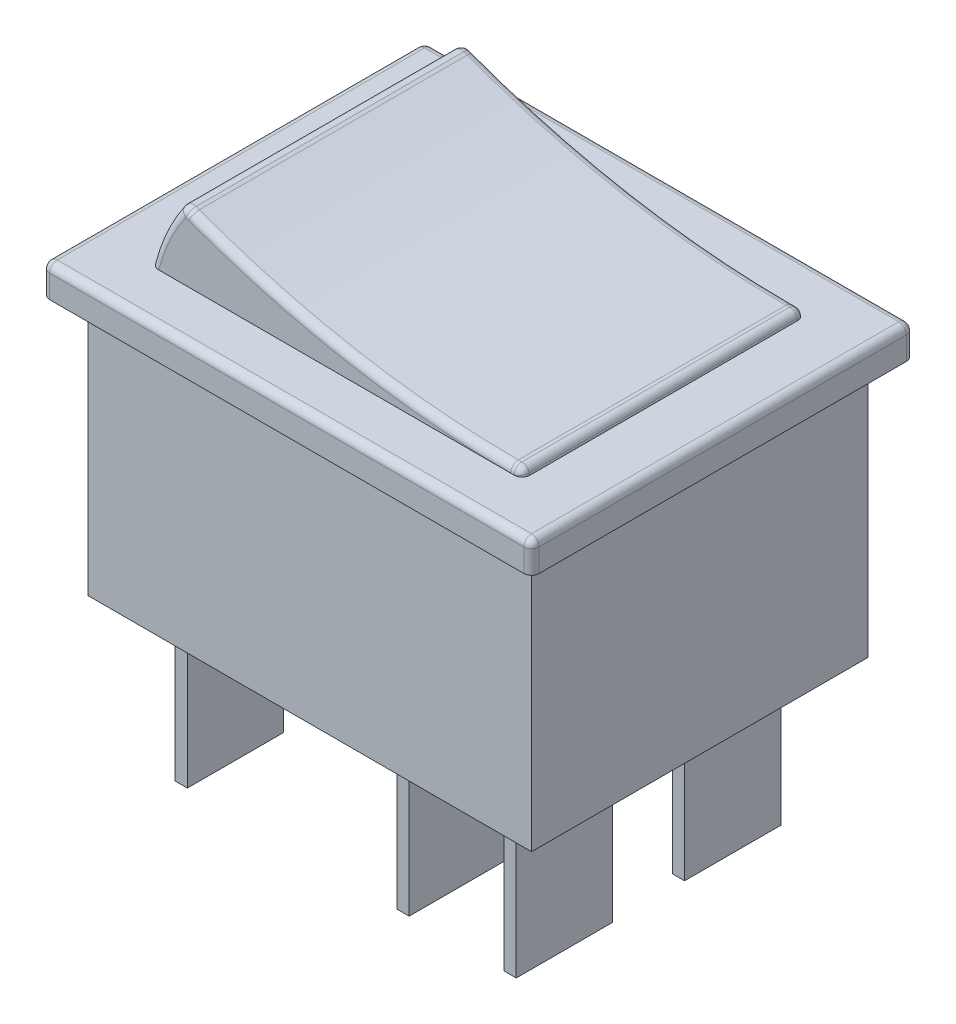
SolidWorks part; units mm, degrees
material "ABS"
ref_plane "Plan de face" through (0, 0, 0) normal (0, 0, 1) x (1, 0, 0)
ref_plane "Plan de dessus" through (0, 0, 0) normal (0, 1, 0) x (1, 0, 0)
ref_plane "Plan de droite" through (0, 0, 0) normal (1, 0, 0) x (0, 0, -1)
sketch "Esquisse1" plane through (0, 0, 0) normal (0, 1, 0) x (1, 0, 0)
  line L1 (-16, -12.5) -> (16, -12.5)
  line L2 (-16, -12.5) -> (-16, 12.5)
  line L3 (-16, 12.5) -> (16, 12.5)
  line L4 (16, -12.5) -> (16, 12.5)
  line L5 (-16, -12.5) -> (16, 12.5) construction
  line L6 (-16, 12.5) -> (16, -12.5) construction
  point P0 (0, 0)
  dimension "D1" = 25
  dimension "D2" = 32
extrude "Boss.-Extru.1" add sketch "Esquisse1" along normal blind 2
fillet "Congé1" radius 0.5 8 edges at (0, 2, 12.5) (-16, 2, 0) (0, 2, -12.5) (16, 2, 0) (16, 1, 12.5) (-16, 1, -12.5) (16, 1, -12.5) (-16, 1, 12.5)
sketch "Esquisse2" plane through (0, 0, 0) normal (0, -1, 0) x (1, 0, 0)
  line L0 (-15.5, 12.5) -> (15.5, 12.5) construction
  line L1 (-14.5, -11) -> (14.5, -11)
  line L2 (-14.5, -11) -> (-14.5, 11)
  line L3 (-14.5, 11) -> (14.5, 11)
  line L4 (14.5, -11) -> (14.5, 11)
  line L5 (-14.5, -11) -> (14.5, 11) construction
  line L6 (-14.5, 11) -> (14.5, -11) construction
  line L7 (-16, -12) -> (-16, 12) construction
  point P0 (0, 0)
  dimension "D1" = 22
  dimension "D2" = 29
  dimension "D3" = 1.5
  dimension "D4" = 1.5
extrude "Boss.-Extru.2" add sketch "Esquisse2" along normal blind 17
sketch "Esquisse3" plane through (0, -17, 0) normal (0, -1, 0) x (1, 0, 0)
  line L0 (-14.5, 0) -> (14.5, 0) construction
  line L1 (-11.15, 8.65) -> (-10.35, 8.65)
  line L2 (-11.15, 8.65) -> (-11.15, 2.35)
  line L3 (-11.15, 2.35) -> (-10.35, 2.35)
  line L4 (-10.35, 8.65) -> (-10.35, 2.35)
  line L5 (10.35, 8.65) -> (11.15, 8.65)
  line L6 (10.35, 8.65) -> (10.35, 2.35)
  line L7 (10.35, 2.35) -> (11.15, 2.35)
  line L8 (11.15, 8.65) -> (11.15, 2.35)
  line L9 (3.35, 8.65) -> (4.15, 8.65)
  line L10 (3.35, 8.65) -> (3.35, 2.35)
  line L11 (3.35, 2.35) -> (4.15, 2.35)
  line L12 (4.15, 8.65) -> (4.15, 2.35)
  line L13 (-14.5, 11) -> (-14.5, -11) construction
  line L14 (14.5, -11) -> (14.5, 11) construction
  line L15 (4.15, -8.65) -> (4.15, -2.35)
  line L16 (3.35, -2.35) -> (4.15, -2.35)
  line L17 (3.35, -8.65) -> (3.35, -2.35)
  line L18 (3.35, -8.65) -> (4.15, -8.65)
  line L19 (11.15, -8.65) -> (11.15, -2.35)
  line L20 (10.35, -2.35) -> (11.15, -2.35)
  line L21 (10.35, -8.65) -> (10.35, -2.35)
  line L22 (10.35, -8.65) -> (11.15, -8.65)
  line L23 (-10.35, -8.65) -> (-10.35, -2.35)
  line L24 (-11.15, -2.35) -> (-10.35, -2.35)
  line L25 (-11.15, -8.65) -> (-11.15, -2.35)
  line L26 (-11.15, -8.65) -> (-10.35, -8.65)
  line L27 (-16, -12) -> (-16, 12) construction
  line L28 (16, 12) -> (16, -12) construction
  dimension "D1" = 0.8
  dimension "D2" = 4.85
  dimension "D3" = 14.5
  dimension "D4" = 21.5
  dimension "D5" = 4.85
  dimension "D6" = 6.3
  dimension "D7" = 11
extrude "Boss.-Extru.3" add sketch "Esquisse3" along normal blind 10 separate body
sketch "Esquisse4" plane through (0, 0, 0) normal (0, 0, 1) x (1, 0, 0)
  line L0 (-15.5, 2) -> (15.5, 2) construction
  line L1 (-12.1347, 2) -> (12.1347, 2)
  line L2 (-9.6791, 6.3189) -> (-9.4605, 6.2379)
  line L3 (11.3859, 2.5) -> (11.619, 2.5)
  arc A0 (12.1347, 2) -> (12.1031, 2.125) centre (0, -1) ccw
  circle A1 centre (0, -1) radius 3.5 construction
  arc A2 (-10.2633, 6.1354) -> (-12.1347, 2) centre (0, -1) ccw
  arc A3 (11.619, 2.5) -> (12.1031, 2.125) centre (11.619, 2) cw
  arc A4 (-9.4605, 6.2379) -> (11.3859, 2.5) centre (11.3859, 62.5) ccw
  arc A5 (-9.6791, 6.3189) -> (-10.2633, 6.1354) centre (-9.8528, 5.85) ccw
  point P16 (-10.0364, 6.4512)
  dimension "D1" = 3
  dimension "D2" = 25
  dimension "D3" = 0.5
  dimension "D5" = 3.85
  dimension "D6" = 60
  dimension "D4" = 0.5
extrude "Boss.-Extru.4" add sketch "Esquisse4" along normal mid plane 18.5 separate body
fillet "Congé2" radius 0.5 14 edges at (12.119, 2.0625, -9.25) (11.9251, 2.3953, -9.25) (-11.3883, 4.1534, -9.25) (-10.0026, 6.327, -9.25) (-9.5698, 6.2784, -9.25) (0.7965, 3.4419, -9.25) (12.119, 2.0625, 9.25) (11.9251, 2.3953, 9.25) (11.5024, 2.5, 9.25) (0.7965, 3.4419, 9.25) (-9.5698, 6.2784, 9.25) (-10.0026, 6.327, 9.25) (11.5024, 2.5, -9.25) (-11.3883, 4.1534, 9.25)
